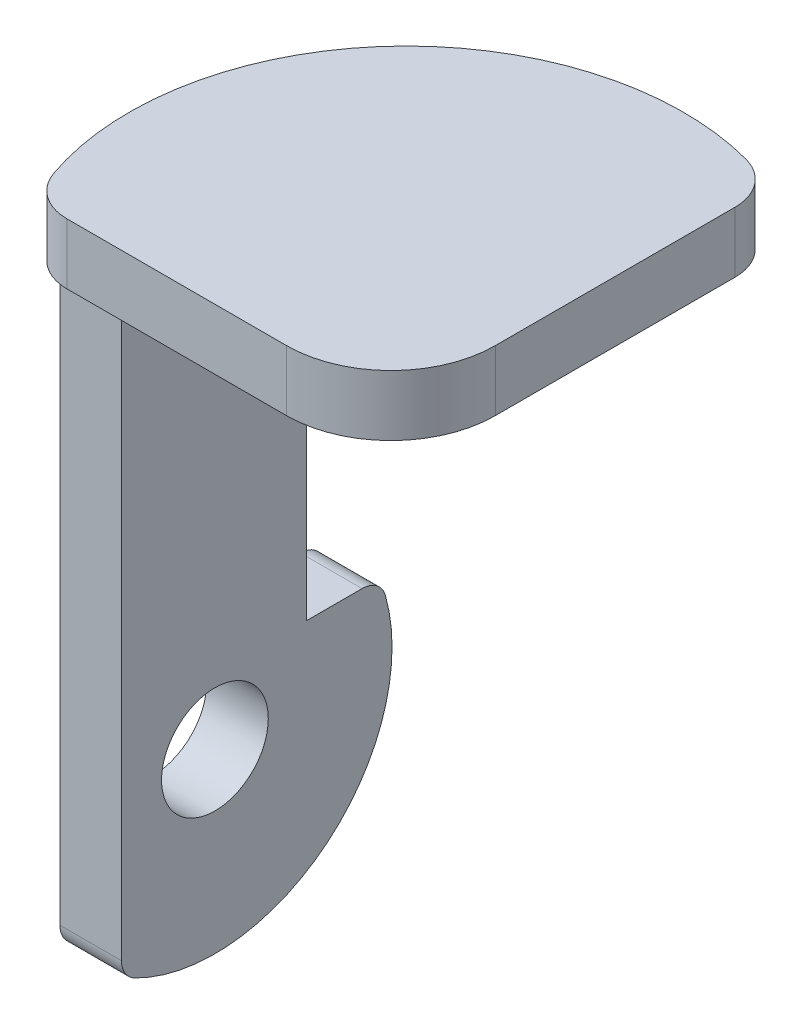
SolidWorks part; units mm, degrees
ref_plane "Front Plane" through (0, 0, 0) normal (0, 0, 1) x (1, 0, 0)
ref_plane "Top Plane" through (0, 0, 0) normal (0, 1, 0) x (1, 0, 0)
ref_plane "Right Plane" through (0, 0, 0) normal (1, 0, 0) x (0, 0, -1)
sketch "Sketch1" plane through (0, 0, 0) normal (0, 1, 0) x (1, 0, 0)
  line L0 (-114.3, 86) -> (0, 86) construction
  line L1 (-114.3, -28.3) -> (-114.3, 86) construction
  line L2 (44.45, 62.7752) -> (44.45, -36.1)
  line L3 (1.45, -79.1) -> (-89.1283, -79.1)
  arc A0 (29.6356, 82.0912) -> (-108.0314, -65.6323) centre (0, -28.3) ccw
  arc A2 (1.45, -79.1) -> (44.45, -36.1) centre (1.45, -36.1) ccw
  arc A3 (44.45, 62.7752) -> (29.6356, 82.0912) centre (24.45, 62.7752) ccw
  arc A4 (-89.1283, -79.1) -> (-108.0314, -65.6323) centre (-89.1283, -59.1) cw
  dimension "D1" = 43
  dimension "D2" = 20
  dimension "D3" = 20
  dimension "D6" = 158.75
  dimension "D4" = 50.8
  dimension "D5" = 114.3
extrude "Boss-Extrude2" add sketch "Sketch1" against normal blind 25
ref_plane "Plane1" through (-110, 0, 0) normal (1, 0, 0) x (0, 0, -1)
ref_plane "Plane2" through (0, 0, 79.1) normal (0, 0, 1) x (1, 0, 0)
sketch "Sketch2" plane through (-110, 0, 0) normal (1, 0, 0) x (0, 0, -1)
  line L0 (-61.1, -215.3696) -> (-61.1, -271.5545)
  line L1 (-79.1, 13.75) -> (-79.1, -13.75) construction
  line L2 (15.1, -188.318) -> (15.1, -25.3696)
  line L3 (15.1, -25.3696) -> (-61.1, -25.3696)
  line L4 (-61.1, -215.3696) -> (-61.1, -25.3696)
  line L8 (15.1, -188.318) -> (38.0485, -188.318)
  circle A0 centre (-22.6, -215.3696) radius 22
  arc A1 (-55.6238, -280.4728) -> (47.6753, -195.6114) centre (-22.6, -215.3696) ccw
  arc A2 (-55.6238, -280.4728) -> (-61.1, -271.5545) centre (-51.1, -271.5545) cw
  arc A3 (47.6753, -195.6114) -> (38.0485, -188.318) centre (38.0485, -198.318) ccw
  point P0 (-3.6009, -120.3696)
  dimension "D1" = 76.2
  dimension "D2" = 18
extrude "Boss-Extrude5" add sketch "Sketch2" along normal blind 25.4 separate body
ref_point "Point1"
ref_axis "Axis1" through (0, 0, 0) along (0, -1, 0)
sketch "Sketch3" plane through (0, 0, 0) normal (0, 1, 0) x (1, 0, 0)
  line L0 (0, 0) -> (0, 38.7564)
ref_plane "Plane3" through (0, 0, 0) normal (1, 0, 0) x (0, 0, -1)
